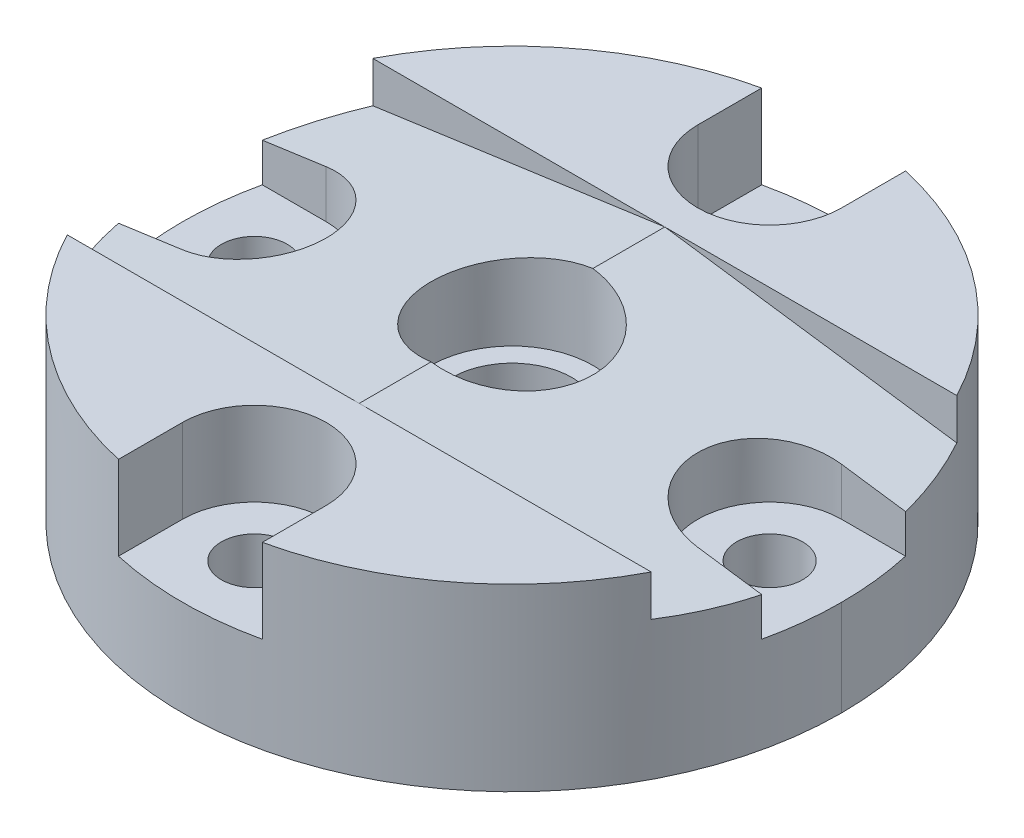
SolidWorks part; units mm, degrees
ref_plane "Piano frontale" through (0, 0, 0) normal (0, 0, 1) x (1, 0, 0)
ref_plane "Piano superiore" through (0, 0, 0) normal (0, 1, 0) x (1, 0, 0)
ref_plane "Piano destro" through (0, 0, 0) normal (1, 0, 0) x (0, 0, -1)
sketch "Schizzo3" plane through (0, 0, 0) normal (0, 0, 1) x (1, 0, 0)
  line L1 (0, 0) -> (-110, 0)
  line L2 (0, 0) -> (0, 30)
  line L3 (0, 30) -> (-110, 30)
  line L4 (-110, 0) -> (-110, 30)
  dimension "D1" = 110
  dimension "D2" = 30
extrude "Estrusione-Estrusione2" add sketch "Schizzo3" along normal blind 55
fillet "Raccordo1" 2 edges at (0, 15, 55) (-110, 15, 55) type full round first side face at (0, 15, 27.5) second side face at (-110, 15, 27.5) middle face at (-55, 15, 55)
sketch "Schizzo6" plane through (0, 0, 0) normal (0, 0, -1) x (-1, 0, 0)
  line L0 (55, 30) -> (0, 22.2703)
  line L1 (0, 30) -> (110, 30) construction
  line L2 (0, 0) -> (0, 30) construction
  line L3 (0, 22.2703) -> (0, 30)
  line L4 (0, 30) -> (55, 30)
  line L5 (55, 30) -> (110, 30)
  line L6 (110, 30) -> (110, 22.2703)
  line L7 (110, 30) -> (110, 0) construction
  line L8 (110, 22.2703) -> (55, 30)
  line M6 (0, 30) -> (0, 0)
  line M8 (110, 0) -> (110, 30)
  line M9 (110, 30) -> (0, 30)
  dimension "D1" = 8
  dimension "D2" = 8
extrude "Taglio-Estrusione1" cut sketch "Schizzo6" against normal blind 25.5 contours L0 M9 M6 | L8 M8 M9 region at (-18.3333, 27.4234, 0) region at (-91.6667, 27.4234, 0)
mirror "Specchia1" about plane through (0, 0, 0) normal (0, 0, 1) of "Raccordo1", "Estrusione-Estrusione2", "Taglio-Estrusione1"
sketch "Schizzo8" plane through (0, 30, 0) normal (0, 1, 0) x (1, 0, 0)
  line L0 (-55, -55) -> (-55, 55) construction
  line L1 (-43, -55) -> (-67, -55)
  line L2 (-67, -55) -> (-67, -43)
  line L3 (-43, -55) -> (-43, -43)
  line L4 (7.7951, 62.7951) -> (-117.7951, -62.7951) construction
  line L5 (10.9291, 0) -> (-120.9291, 0) construction
  line L6 (-67, 55) -> (-67, 43)
  line L7 (-43, 55) -> (-67, 55)
  line L8 (-43, 55) -> (-43, 43)
  line L9 (0, 12) -> (0, -12)
  line L10 (0, 12) -> (-12, 12)
  line L11 (0, -12) -> (-12, -12)
  line L12 (-110, -12) -> (-98, -12)
  line L13 (-110, 12) -> (-110, -12)
  line L14 (-110, 12) -> (-98, 12)
  arc A0 (-103.7314, -25.5) -> (-6.2686, -25.5) centre (-55, 0) ccw construction
  arc A1 (-6.2686, 25.5) -> (-103.7314, 25.5) centre (-55, 0) ccw construction
  arc A2 (-67, -43) -> (-43, -43) centre (-55, -43) cw
  arc A3 (-67, 43) -> (-43, 43) centre (-55, 43) ccw
  arc A4 (-12, -12) -> (-12, 12) centre (-12, 0) cw
  arc A5 (-98, -12) -> (-98, 12) centre (-98, 0) ccw
  point P16 (-55, 0)
  point P19 (-55, 0)
  dimension "D2" = 12
  dimension "D1" = 12
  dimension "D3" = 12
  dimension "D4" = 90
  dimension "D5" = 45
extrude "Taglio-Estrusione2" cut sketch "Schizzo8" against normal blind 14
sketch "Schizzo9" plane through (0, 16, 0) normal (0, 1, 0) x (1, 0, 0)
  line L0 (0, 0) -> (-110, 0) construction
  line L1 (-55, 0) -> (-55, -50000) construction
  line L2 (-55, 0) -> (-35410.3391, -35355.3391) construction
  circle A0 centre (-12, 0) radius 5.5
  arc A1 (-12, 12) -> (-12, -12) centre (-12, 0) ccw construction
  circle A2 centre (-98, 0) radius 5.5
  circle A3 centre (-55, -43) radius 5.5
  circle A4 centre (-55, 43) radius 5.5
  point P11 (-55, 0)
  dimension "D1" = 11
  dimension "D2" = 45
sketch "Schizzo10" plane through (0, 16, 0) normal (0, 1, 0) x (1, 0, 0)
  line L0 (0, 0) -> (-110, 0) construction
  circle A0 centre (-55, 0) radius 13.5
  dimension "D1" = 27
extrude "Taglio-Estrusione3" cut sketch "Schizzo9" against normal through all
extrude "Taglio-Estrusione5" cut sketch "Schizzo10" along normal through all
sketch "Schizzo11" plane through (0, 16, 0) normal (0, 1, 0) x (1, 0, 0)
  circle A0 centre (-55, 0) radius 10
  circle A1 centre (-55, 0) radius 13.5 construction
  dimension "D1" = 20
extrude "Taglio-Estrusione6" cut sketch "Schizzo11" against normal through all
